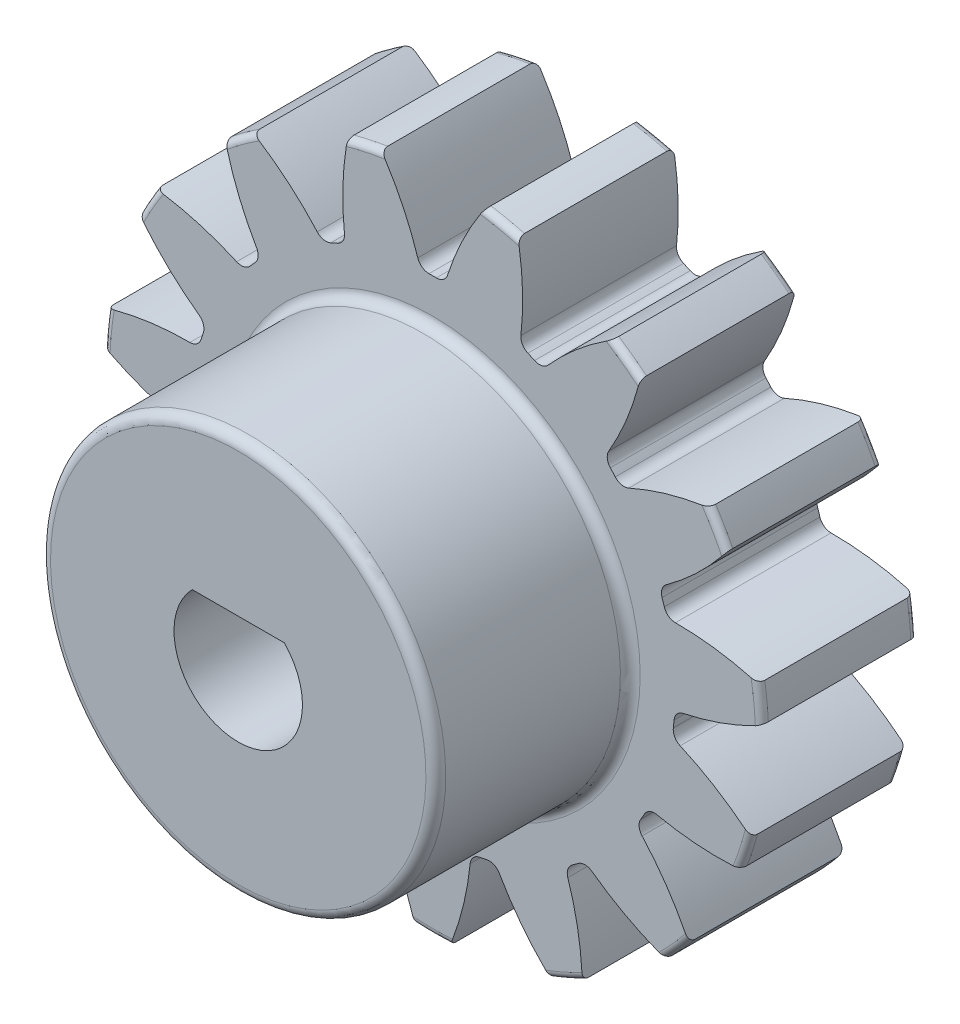
SolidWorks part; units mm, degrees
ref_plane "Front Plane" through (0, 0, 0) normal (0, 0, 1) x (1, 0, 0)
ref_plane "Top Plane" through (0, 0, 0) normal (0, 1, 0) x (1, 0, 0)
ref_plane "Right Plane" through (0, 0, 0) normal (1, 0, 0) x (0, 0, -1)
sketch "Sketch1" plane through (0, 0, 0) normal (0, 0, 1) x (1, 0, 0)
  line L0 (-190.5, 0) -> (190.5, 0) construction
  circle A0 centre (0, 0) radius 8.4709 construction
  circle A1 centre (0, 0) radius 7.4676 construction
  circle A2 centre (0, 0) radius 6.2306 construction
  circle A3 centre (0, 0) radius 5.842 construction
  circle A4 centre (0, 0) radius 3.9688 construction
  dimension "D1" = 2.2403
sketch "Sketch2" plane through (0, 0, 0) normal (1, 0, 0) x (0, 0, -1)
  line L0 (0, 0) -> (-4.0005, 0) construction
  line L1 (-4.0005, 0) -> (-8.9992, 0) construction
  dimension "Overall Width" = 8.9992
  dimension "Face Width" = 4.0005
sketch "Sketch4" plane through (0, 0, 0) normal (1, 0, 0) x (0, 0, -1)
  line L0 (-8.9992, 3.9688) -> (-8.9992, 5.842)
  line L1 (-8.9992, 5.842) -> (-4.0005, 5.842)
  line L2 (-4.0005, 5.842) -> (-4.0005, 8.4709)
  line L3 (-4.0005, 8.4709) -> (0, 8.4709)
  line L4 (0, 8.4709) -> (0, 3.9688)
  line L5 (-4.0005, 5.842) -> (-4.0005, 0) construction
  line L6 (0, 8.4709) -> (0, -8.4709) construction
  line L7 (-4.0005, 5.842) -> (0, 5.842) construction
  line L12 (-8.9992, 3.9688) -> (0, 3.9688)
revolve "Revolve1" add sketch "Sketch4" angle 360 about L1
fillet "Fillet2" radius 0.1694 4 edges at (0, 5.842, 8.9992) (0, 5.842, 4.0005) (0, 8.4709, 4.0005) (0, 8.4709, 0)
sketch "Sketch7" plane through (0, 0, 4.0005) normal (0, 0, 1) x (1, 0, 0)
  line L0 (0, 0) -> (0, 8.4709) construction
  line L1 (0.7806, 7.4267) -> (1.245, 8.3789) construction
  line L3 (1.7612, 8.2858) -> (1.5526, 7.3044) construction
  line L4 (1.5526, 7.3044) -> (1.2954, 6.0945) construction
  line L5 (0, 0) -> (1.2954, 6.0945) construction
  line L6 (0.7806, 7.4267) -> (0, 0) construction
  line L7 (0.7806, 7.4267) -> (0.8854, 8.4245) construction
  line L8 (0.7806, 7.4267) -> (0, 0) construction
  circle A0 centre (0, 0) radius 8.4709 construction
  arc A1 (-0.0938, 6.2299) -> (0.0938, 6.2299) centre (0, 0) cw
  circle A2 centre (0, 0) radius 6.2306 construction
  arc A3 (-0.7806, 7.4267) -> (0.7806, 7.4267) centre (0, 0) cw construction
  circle A4 centre (0, 0) radius 7.4676 construction
  arc A5 (2.1907, 8.1827) -> (1.3269, 8.3663) centre (0, 0) ccw construction
  arc A6 (0.7806, 7.4267) -> (2.3076, 7.1021) centre (0, 0) cw construction
  arc A7 (-1.3269, 8.3663) -> (1.3269, 8.3663) centre (0, 0) cw
  arc A8 (0.3827, 6.4372) -> (1.3269, 8.3663) centre (7.4924, 4.1531) cw
  arc A9 (-0.3827, 6.4372) -> (-1.3269, 8.3663) centre (-7.4924, 4.1531) ccw
  arc A10 (-0.0938, 6.2299) -> (-0.3827, 6.4372) centre (-0.0983, 6.5286) cw
  arc A11 (0.0938, 6.2299) -> (0.3827, 6.4372) centre (0.0983, 6.5286) ccw
  point P26 (-0.3173, 6.2225)
  point P29 (0.3173, 6.2225)
  dimension "D4" = 0.2987
  dimension "D5" = 7.4676
  dimension "D3" = 20
  dimension "D1" = 3.128
  dimension "D2" = 1.564
extrude "Cut-Extrude2" cut sketch "Sketch7" against normal through all
pattern_circular "CirPattern1" count 15 over 360 about axis through (0, 0, 8.9992) along (0, 0, -1) of "Cut-Extrude2"
sketch "Sketch8" plane through (0, 0, 8.9992) normal (0, 0, 1) x (1, 0, 0)
  line L1 (-1.1836, 1.151) -> (1.1836, 1.151)
  circle A1 centre (0, 0) radius 5.08
  arc A2 (-1.1836, 1.151) -> (1.1836, 1.151) centre (0, 0) ccw
  dimension "D1" = 3.302
  dimension "D2" = 10.16
  dimension "D3" = 1.151
extrude "Boss-Extrude1" add sketch "Sketch8" against normal up to surface (8.9992 mm away) up to face at (0, 0, 0)
sketch "Sketch9" plane through (0, 0, 8.9992) normal (0, 0, 1) x (1, 0, 0)
  circle A0 centre (0, 0) radius 5.08
  circle A1 centre (0, 0) radius 11.0522
  dimension "D1" = 10.16
extrude "Cut-Extrude3" cut sketch "Sketch9" against normal up to surface (4.9987 mm away) up to face at (0, 0, 4.0005)
fillet "Fillet3" radius 0.254 2 edges at (0, -5.08, 4.0005) (5.08, 0, 8.9992)
sketch "Sketch10" plane through (0, 0, 0) normal (0, 0, -1) x (-1, 0, 0)
  circle A0 centre (0, 0) radius 8.7122
  circle A1 centre (0, 0) radius 6.2306
  circle A2 centre (0, 0) radius 7.4714
  dimension "D1" = 14.9428
  dimension "D2" = 12.4612
  dimension "D3" = 17.4244
sketch "Sketch11" plane through (0, 0, 0) normal (0, 0, -1) x (-1, 0, 0)
  line L0 (-1.1836, 1.151) -> (1.1836, 1.151) construction
  line L1 (-1.1836, 1.151) -> (1.1836, 1.151)
  line L2 (0, 1.151) -> (0, -3.2731)
ref_plane "Plane1" through (0, 0, 0) normal (1, 0, 0) x (0, -1, 0)
sketch "Sketch12" plane through (0, 0, 0) normal (1, 0, 0) x (0, -1, 0)
  line L0 (0, 0) -> (0, 6.5563)
ref_axis "Axis1" through (0, 0, 0) along (0, 0, -1)
equation "\"D1@Sketch1\"=2.25*(\"Pitch Dia.@Sketch1\"/\"Number of Teeth@Sketch1\")"
equation "\"D1@Fillet2\" = \"Addendum Circle@Sketch1\" * .01"
equation "\"D1@Sketch7\"=3.14159*(\"Pitch Dia.@Sketch1\"/\"Number of Teeth@Sketch1\")"
equation "\"D2@Sketch7\"=\"D1@Sketch7\"/2"
equation "\"D4@Sketch7\"=\"D1@Sketch7\"*.0955"
equation "\"D5@Sketch7\"=\"Pitch Dia.@Sketch1\"/2"
equation "\"D1@Sketch10\"=(\"D3@Sketch10\"+\"D2@Sketch10\")/2"
